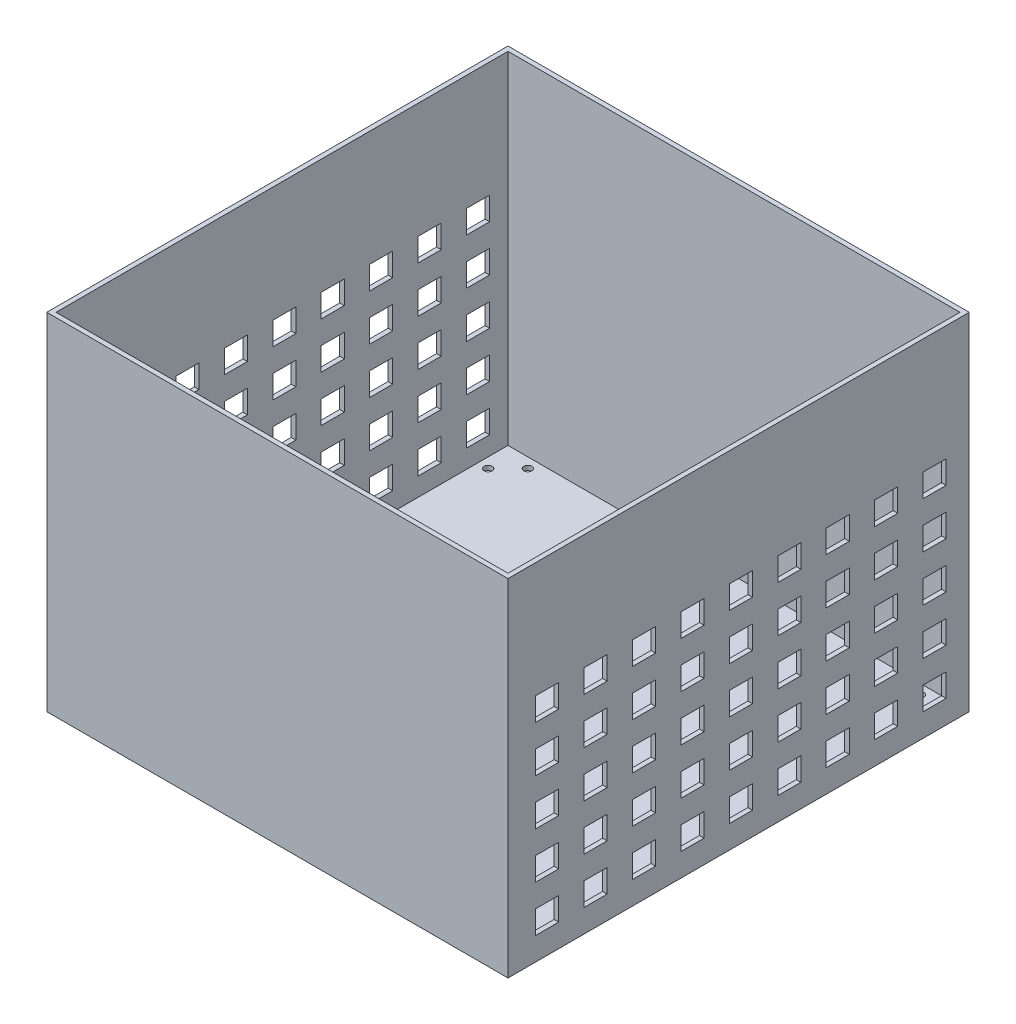
SolidWorks part; units mm, degrees
ref_plane "前视基准面" through (0, 0, 0) normal (0, 0, 1) x (1, 0, 0)
ref_plane "上视基准面" through (0, 0, 0) normal (0, 1, 0) x (1, 0, 0)
ref_plane "右视基准面" through (0, 0, 0) normal (1, 0, 0) x (0, 0, -1)
sketch "草图1" plane through (0, 0, 0) normal (0, 1, 0) x (1, 0, 0)
  line L1 (0, 0) -> (200, 0)
  line L2 (0, 0) -> (0, 200)
  line L3 (0, 200) -> (200, 200)
  line L4 (200, 0) -> (200, 200)
  dimension "D1" = 200
  dimension "D2" = 200
extrude "凸台-拉伸1" add sketch "草图1" along normal blind 150
shell "抽壳1" thickness 2 removed face at (100, 150, -100)
sketch "草图2" plane through (0, 0, 0) normal (-1, 0, 0) x (0, 0, 1)
  line L0 (-185, 10) -> (-185, 0) construction
  line L1 (-190, 10) -> (-180, 10)
  line L2 (-190, 10) -> (-190, 20)
  line L3 (-190, 20) -> (-180, 20)
  line L4 (-180, 10) -> (-180, 20)
  line L5 (-200, 0) -> (0, 0) construction
  line L6 (-190, 15) -> (-200, 15) construction
  line L7 (-200, 150) -> (-200, 0) construction
  dimension "D1" = 10
  dimension "D2" = 10
  dimension "D3" = 10
  dimension "D4" = 10
extrude "切除-拉伸1" cut sketch "草图2" against normal blind 474
pattern_linear "阵列(线性)1" count 5 spacing 20 along (0, 1, 0) count 9 spacing 21 along (0, 0, 1) of "切除-拉伸1"
sketch "草图3" plane through (0, 0, 0) normal (0, -1, 0) x (-1, 0, 0)
  line L0 (0, 187.2721) -> (0, 200) construction
  line L1 (0, 200) -> (0, 0) construction
  line L2 (0, 200) -> (-12.7279, 200) construction
  line L3 (-200, 200) -> (0, 200) construction
  line L4 (-12.7279, 200) -> (0, 187.2721) construction
  line L5 (-6.364, 193.636) -> (-6.364, 50193.636) construction
  line L6 (-6.364, 193.636) -> (-50006.364, 193.636) construction
  line L7 (-200, 200) -> (-187.2721, 200) construction
  line L8 (-187.2721, 200) -> (-200, 187.2721) construction
  line L9 (-200, 0) -> (-200, 200) construction
  line L10 (-200, 187.2721) -> (-200, 200) construction
  line L11 (-193.636, 193.636) -> (-193.636, 50193.636) construction
  line L12 (-200, 0) -> (-187.2721, 0) construction
  line L13 (0, 0) -> (-200, 0) construction
  line L14 (-187.2721, 0) -> (-200, 12.7279) construction
  line L15 (-200, 12.7279) -> (-200, 0) construction
  line L16 (-193.636, 6.364) -> (-50193.636, 6.364) construction
  circle A0 centre (-6.364, 185) radius 1.75
  circle A1 centre (-15, 193.636) radius 1.75
  circle A2 centre (-185, 193.636) radius 1.75
  circle A3 centre (-193.636, 185) radius 1.75
  circle A4 centre (-15, 6.364) radius 1.75
  circle A5 centre (-6.364, 15) radius 1.75
  circle A6 centre (-185, 6.364) radius 1.75
  circle A7 centre (-193.636, 15) radius 1.75
  point P10 (-6.364, 193.636)
  point P27 (-193.636, 193.636)
  point P38 (-193.636, 6.364)
  dimension "D3" = 3.5
  dimension "D5" = 15
  dimension "D9" = 15
  dimension "D12" = 15
  dimension "D13" = 15
  dimension "D14" = 15
  dimension "D15" = 15
  dimension "D1" = 18
  dimension "D2" = 45
  dimension "D4" = 15
  dimension "D6" = 18
  dimension "D7" = 45
  dimension "D8" = 15
  dimension "D10" = 18
  dimension "D11" = 45
extrude "切除-拉伸2" cut sketch "草图3" against normal through all
